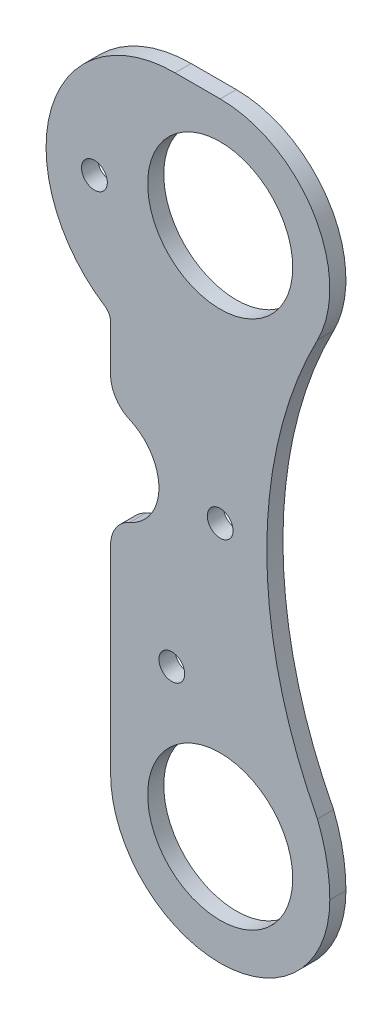
SolidWorks part; units mm, degrees
material "6061 Alloy"
ref_plane "Front Plane" through (0, 0, 0) normal (0, 0, 1) x (1, 0, 0)
ref_plane "Top Plane" through (0, 0, 0) normal (0, 1, 0) x (1, 0, 0)
ref_plane "Right Plane" through (0, 0, 0) normal (1, 0, 0) x (0, 0, -1)
sketch "Sketch1" plane through (0, 0, 0) normal (0, 0, 1) x (1, 0, 0)
  line L0 (0, 0) -> (0, -101.6) construction
  line L1 (21.59, -120.5575) -> (-21.59, -120.5575) construction
  line L2 (-8.89, 25.4) -> (8.89, 25.4)
  line L3 (-21.59, 12.7) -> (-21.59, -117.7751)
  line L5 (21.59, 12.7) -> (21.59, -117.7751)
  line L9 (-23.3829, -122.6853) -> (-33.2033, -134.3394)
  line L10 (-36.322, 25.4) -> (20.828, 25.4) construction
  line L11 (-36.322, 25.4) -> (-36.322, -203.2) construction
  line L12 (-36.322, -203.2) -> (20.828, -203.2) construction
  line L13 (20.828, 25.4) -> (20.828, -203.2) construction
  line L15 (-7.9527, -155.6168) -> (19.7971, -122.6853)
  line L16 (-32.4392, -143.2871) -> (-16.9004, -156.3809)
  circle A0 centre (0, 0) radius 38.1 construction
  circle A1 centre (0, -101.6) radius 38.1 construction
  circle A2 centre (0, 0) radius 14.2875
  circle A3 centre (0, -101.6) radius 14.2875
  arc A6 (8.89, 25.4) -> (21.59, 12.7) centre (8.89, 12.7) cw
  arc A7 (-8.89, 25.4) -> (-21.59, 12.7) centre (-8.89, 12.7) ccw
  circle A10 centre (-18.5321, -142.5501) radius 2.54
  arc A13 (-23.3829, -122.6853) -> (-21.59, -117.7751) centre (-29.21, -117.7751) ccw
  arc A14 (19.7971, -122.6853) -> (21.59, -117.7751) centre (13.97, -117.7751) ccw
  arc A15 (-16.9004, -156.3809) -> (-7.9527, -155.6168) centre (-12.8086, -151.525) ccw
  arc A16 (-33.2033, -134.3394) -> (-32.4392, -143.2871) centre (-28.3474, -138.4312) ccw
  circle A17 centre (0, -50.8) radius 2.54
  point P13 (-192.705, 39.2708)
  point P20 (21.59, 25.4)
  point P23 (-21.59, 25.4)
  point P31 (-36.322, -138.0404)
  dimension "D2" = 76.2
  dimension "D3" = 76.2
  dimension "D4" = 28.575
  dimension "D5" = 28.575
  dimension "D10" = 228.6
  dimension "D11" = 36.322
  dimension "D13" = 5.08
  dimension "D19" = 6.35
  dimension "D20" = 7.62
  dimension "D21" = 12.7
  dimension "D22" = 5.08
  dimension "D1" = 101.6
  dimension "D6" = 43.18
  dimension "D7" = 21.59
  dimension "D8" = 25.4
  dimension "D9" = 57.15
  dimension "D12" = 25.4
  dimension "D14" = 33.02
  dimension "D15" = 16.51
  dimension "D16" = 21.59
  dimension "D17" = 9.525
  dimension "D18" = 18.9575
extrude "Boss-Extrude1" add sketch "Sketch1" along normal blind 3.175
sketch "Sketch2" plane through (0, 0, 0) normal (0, 0, 1) x (1, 0, 0)
  line L0 (-21.59, -41.275) -> (-21.59, -60.325)
  line L1 (0, 0) -> (0, -101.6) construction
  line L4 (21.59, -117.7751) -> (21.59, 12.7) construction
  line L5 (-21.59, -50.8) -> (97.79, -50.8) construction
  line L6 (-21.59, 12.7) -> (-21.59, -117.7751) construction
  line L7 (0, 0) -> (-39.9512, 0) construction
  line L9 (16.51, -115.5122) -> (-17.5013, -155.8745)
  line L10 (-32.4392, -143.2871) -> (-16.9004, -156.3809) construction
  line L11 (-7.9527, -155.6168) -> (19.7971, -122.6853) construction
  line L13 (27.94, -121.6567) -> (-7.7896, -164.0581)
  line L14 (-7.7896, -164.0581) -> (-17.5013, -155.8745)
  line L15 (27.94, -121.6567) -> (27.94, 0)
  line L16 (27.94, 0) -> (21.59, 0)
  arc A1 (19.1591, -91.6472) -> (19.1591, -9.9528) centre (97.79, -50.8) cw
  arc A2 (-21.59, -60.325) -> (-21.59, -41.275) centre (-21.59, -50.8) ccw
  arc A3 (21.59, 0) -> (19.1591, -9.9528) centre (0, 0) cw
  arc A4 (21.59, -101.6) -> (19.1591, -91.6472) centre (0, -101.6) ccw
  arc A5 (21.59, -101.6) -> (16.51, -115.5122) centre (0, -101.6) cw
  dimension "D2" = 12.7
  dimension "D3" = 50.8
  dimension "D4" = 6.35
  dimension "D1" = 76.2
  dimension "D5" = 19.05
extrude "Cut-Extrude1" cut sketch "Sketch2" along normal through all contours A1 A3 L16 L15 L13 L14 L9 A5 A4 | L0 A2
sketch "Sketch3" plane through (0, 0, 3.175) normal (0, 0, 1) x (1, 0, 0)
  line L0 (-27.3514, -127.3948) -> (-36.0255, -137.6886)
  line L3 (-27.3514, -127.3948) -> (-7.5576, -144.074)
  line L4 (-23.3829, -122.6853) -> (-33.2033, -134.3394) construction
  line L5 (16.51, -115.5122) -> (-17.5013, -155.8745) construction
  line L7 (-35.4064, -144.9387) -> (-24.4031, -154.2106)
  line L8 (-23.3829, -122.6853) -> (-33.2033, -134.3394) construction
  line L9 (-7.5576, -144.074) -> (-15.4554, -153.4465)
  line L10 (-32.4392, -143.2871) -> (-17.5013, -155.8745) construction
  circle A2 centre (-18.5321, -142.5501) radius 2.54
  circle A3 centre (-18.5321, -142.5501) radius 2.54 construction
  arc A5 (-36.0255, -137.6886) -> (-35.4064, -144.9387) centre (-32.0909, -141.0041) ccw
  arc A6 (-24.4031, -154.2106) -> (-15.4554, -153.4465) centre (-20.3113, -149.3547) ccw
  dimension "D2" = 6.35
  dimension "D3" = 5.1453
  dimension "D1" = 3.175
fillet "Fillet3" radius 6.35 2 edges at (-21.59, -41.275, 1.5875) (-21.59, -60.325, 1.5875)
extrude "Boss-Extrude3" add sketch "Sketch3" against normal blind 3.175
sketch "Sketch6" plane through (0, 0, 3.175) normal (0, 0, 1) x (1, 0, 0)
  line L0 (-35.4064, -144.9387) -> (-63.6204, -121.1641)
  line L1 (-63.6204, -121.1641) -> (-51.345, -106.5965)
  line L2 (-51.345, -106.5965) -> (-27.0656, -127.0555)
  line L4 (-35.4064, -144.9387) -> (-24.4031, -154.2106) construction
  line L5 (-23.3829, -122.6853) -> (-36.0255, -137.6886) construction
  line L6 (-35.4064, -144.9387) -> (-27.0656, -127.0555)
  circle A0 centre (-52.6268, -117.9721) radius 2.54
  dimension "D4" = 5.08
  dimension "D1" = 31.75
  dimension "D2" = 9.525
  dimension "1" = 19.05
  dimension "D3" = 6.35
extrude "Boss-Extrude4" add sketch "Sketch6" against normal blind 3.175
fillet "Fillet2" radius 6.35 3 edges at (-63.6204, -121.1641, 1.5875) (-51.345, -106.5965, 1.5875) (-27.0656, -127.0555, 1.5875)
sketch "Sketch7" plane through (0, 0, 3.175) normal (0, 0, 1) x (1, 0, 0)
  line L0 (-21.59, 12.7) -> (-21.59, -36.2503) construction
  line L1 (21.59, 0) -> (21.59, 12.7) construction
  line L2 (-21.59, 0) -> (21.59, 0) construction
  line L3 (-21.59, 0) -> (-21.59, 31.75)
  line L4 (-21.59, 31.75) -> (21.59, 31.75)
  line L5 (21.59, 31.75) -> (21.59, 0)
  line L6 (8.89, 25.4) -> (-8.89, 25.4) construction
  arc A0 (-21.59, 0) -> (21.59, 0) centre (0, 0) cw
  dimension "D1" = 6.35
extrude "Cut-Extrude2" cut sketch "Sketch7" against normal through all
sketch "Sketch10" plane through (0, 0, 3.175) normal (0, 0, 1) x (1, 0, 0)
  line L0 (16.51, -115.5122) -> (-17.5013, -155.8745) construction
  line L1 (-18.1519, -155.3263) -> (-17.3615, -157.512)
  line L2 (-17.3615, -157.512) -> (-14.3757, -156.4323)
  line L3 (-14.3757, -156.4323) -> (-15.4554, -153.4465)
  line L5 (-18.1519, -155.3263) -> (-17.5013, -155.8745) construction
  circle A0 centre (-20.3113, -149.3547) radius 6.35 construction
  arc A1 (-24.4031, -154.2106) -> (-18.1519, -155.3263) centre (-20.3113, -149.3547) ccw construction
  arc A2 (-18.1519, -155.3263) -> (-15.4554, -153.4465) centre (-20.3113, -149.3547) ccw
  dimension "D1" = 3.175
  dimension "D2" = 30
extrude "Cut-Extrude3" cut sketch "Sketch10" against normal through all
sketch "Sketch12" plane through (0, 0, 3.175) normal (0, 0, 1) x (1, 0, 0)
  line L0 (-21.59, -65.3497) -> (-21.59, -117.7751) construction
  line L1 (-21.59, -101.6) -> (-72.39, -101.6)
  line L2 (-72.39, -101.6) -> (-72.39, -165.1)
  line L3 (-72.39, -165.1) -> (16.51, -165.1)
  line L4 (16.51, -165.1) -> (16.51, -115.5122)
  arc A2 (16.51, -115.5122) -> (-21.59, -101.6) centre (0, -101.6) cw
  dimension "D1" = 63.5
  dimension "D2" = 88.9
extrude "Cut-Extrude4" cut sketch "Sketch12" against normal through all
sketch "Sketch15" plane through (0, 0, 3.175) normal (0, 0, 1) x (1, 0, 0)
  line L0 (-21.59, 0) -> (-21.59, -36.2503) construction
  line L5 (-21.59, -29.21) -> (-21.59, 0)
  line L7 (0, 21.59) -> (-16.6076, 6.9565)
  line L8 (-16.6076, 6.9565) -> (-12.5785, -28.9408)
  line L9 (-8.89, 21.59) -> (0, 21.59)
  arc A0 (-12.5785, -28.9408) -> (-34.29, -3.81) centre (-8.89, -3.81) cw
  arc A1 (-8.89, 21.59) -> (-34.29, -3.81) centre (-8.89, -3.81) ccw
  circle A2 centre (-24.765, -3.81) radius 2.54
  arc A3 (19.1591, -9.9528) -> (-21.59, 0) centre (0, 0) ccw construction
  arc M10 (19.1591, -9.9528) -> (-21.59, 0) centre (0, 0) ccw
  line M11 (-21.59, 0) -> (-21.59, -36.2503)
  dimension "D1" = 12.7
  dimension "D4" = 3.175
  dimension "D3" = 5.08
  dimension "D2" = 25.4
extrude "Boss-Extrude8" add sketch "Sketch15" against normal blind 3.175 contours L9 A1 A0 A2 M11 M10 region at (-24.9677, -0.0937, 3.175)
fillet "Fillet4" radius 2.54 1 edges at (-21.59, -25.807, 1.5875)
sketch "Sketch16" plane through (0, 0, 3.175) normal (0, 0, 1) x (1, 0, 0)
  line L1 (0, -102.5377) -> (0, -93.0735) construction
  line L2 (0, -101.6) -> (-11.1927, -101.6) construction
  line L4 (-21.59, -101.6) -> (-1.4895, -121.7005)
  line L5 (-1.4895, -121.7005) -> (4.5179, -121.7005)
  line L6 (4.5179, -121.7005) -> (21.59, -101.6)
  line L7 (-21.59, -65.3497) -> (-21.59, -101.6) construction
  line L8 (-21.59, -101.6) -> (-21.59, -104.2391)
  line L9 (21.59, -101.6) -> (21.59, -104.2391)
  arc A0 (-21.59, -104.2391) -> (21.59, -104.2391) centre (0, -104.2391) ccw
  arc A1 (-21.59, -101.6) -> (19.1591, -91.6472) centre (0, -101.6) ccw construction
  dimension "D1" = 2.6391
extrude "Boss-Extrude9" add sketch "Sketch16" against normal through all contours L6 L9 A0 L8 L4 L5
sketch "Sketch17" plane through (0, 0, 3.175) normal (0, 0, 1) x (1, 0, 0)
  circle A0 centre (0, -101.6) radius 14.2875
  circle A1 centre (0, -101.6) radius 14.2875 construction
extrude "Boss-Extrude10" add sketch "Sketch17" against normal through all
sketch "Sketch19" plane through (0, 0, 3.175) normal (0, 0, 1) x (1, 0, 0)
  line L0 (21.59, -104.2391) -> (21.59, -95.9079) construction
  line L1 (19.1591, -91.6472) -> (21.59, -91.6472)
  line L2 (21.59, -91.6472) -> (21.59, -104.2391)
  arc A0 (19.1591, -91.6472) -> (21.59, -104.2391) centre (-12.2375, -104.2391) cw
extrude "Cut-Extrude5" cut sketch "Sketch19" against normal through all
sketch "Sketch20" plane through (0, 0, 3.175) normal (0, 0, 1) x (1, 0, 0)
  circle A0 centre (0, -104.2391) radius 14.2875
  arc A1 (-21.59, -104.2391) -> (21.59, -104.2391) centre (0, -104.2391) ccw construction
  dimension "D1" = 28.575
extrude "Cut-Extrude6" cut sketch "Sketch20" against normal through all
sketch "Sketch21" plane through (0, 0, 3.175) normal (0, 0, 1) x (1, 0, 0)
  circle A0 centre (-9.525, -80.01) radius 2.54
  circle A1 centre (0, -50.8) radius 2.54 construction
  dimension "D1" = 29.21
  dimension "D2" = 9.525
extrude "Cut-Extrude7" cut sketch "Sketch21" against normal through all
